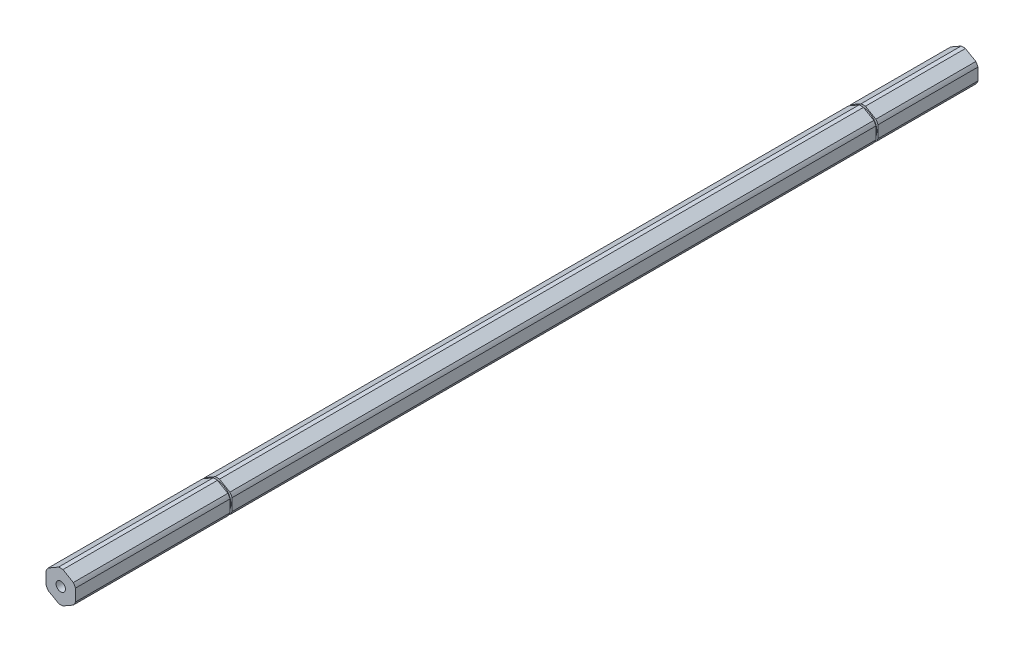
SolidWorks part; units mm, degrees
material "6061-T6 (SS)"
ref_plane "Front Plane" through (0, 0, 0) normal (0, 0, 1) x (1, 0, 0)
ref_plane "Top Plane" through (0, 0, 0) normal (0, 1, 0) x (1, 0, 0)
ref_plane "Right Plane" through (0, 0, 0) normal (1, 0, 0) x (0, 0, -1)
sketch "Sketch1" plane through (0, 0, 0) normal (0, 0, 1) x (1, 0, 0)
  line L1 (0, 7.3323) -> (-6.35, 3.6662)
  line L2 (-6.35, 3.6662) -> (-6.35, -3.6662)
  line L3 (-6.35, -3.6662) -> (0, -7.3323)
  line L4 (0, -7.3323) -> (6.35, -3.6662)
  line L5 (6.35, -3.6662) -> (6.35, 3.6662)
  line L6 (6.35, 3.6662) -> (0, 7.3323)
  circle A0 centre (0, 0) radius 6.35 construction
  circle A1 centre (0, 0) radius 6.858
  dimension "D1" = 12.7
  dimension "D2" = 13.716
extrude "Boss-Extrude1" add sketch "Sketch1" along normal mid plane 388.6403 contours L5 A1 L6 L1 L2 L3 L4 region at (0, 0, 0)
sketch "Sketch2" plane through (0, 0, 194.3202) normal (0, 0, 1) x (1, 0, 0)
  circle A0 centre (0, 0) radius 2.0193
  dimension "D1" = 4.0386
extrude "Cut-Extrude1" [suppressed] cut sketch "Sketch2" against normal through all
sketch "Sketch4" [suppressed] plane through (0, 0, 0) normal (0, 1, 0) x (1, 0, 0)
  line L0 (-2.0193, -194.3202) -> (2.0193, -194.3202) construction
  line L5 (-0.9317, -194.3202) -> (0.9317, -194.3202) construction
  line L7 (9.0297, 151.2672) -> (5.8547, 151.2672)
  line L8 (9.0297, 151.2672) -> (9.0297, 150.3782)
  line L9 (9.0297, 150.3782) -> (5.8547, 150.3782)
  line L10 (5.8547, 151.2672) -> (5.8547, 150.3782)
  line L11 (5.8547, -127.7722) -> (9.0297, -127.7722)
  line L12 (0, 194.3202) -> (0, -194.3202) construction
  line L13 (2.0193, 194.3202) -> (-2.0193, 194.3202) construction
  line L14 (5.8547, -127.7722) -> (5.8547, -126.8832)
  line L15 (5.8547, -126.8832) -> (9.0297, -126.8832)
  line L16 (9.0297, -127.7722) -> (9.0297, -126.8832)
  dimension "D1" = 0.889
  dimension "D2" = 388.6403
  dimension "D3" = 5.8547
  dimension "D4" = 43.053
  dimension "D5" = 3.175
  dimension "D6" = 3.175
  dimension "D7" = 0.889
  dimension "D8" = 66.548
revolve "Cut-Revolve4" [suppressed] cut sketch "Sketch4" angle 360 about L12
hole_wizard "#10-32 Tapped Hole1" positions "3DSketch1" profile "Sketch5" tap size "#10-32" standard "ANSI Inch"
sketch3d "3DSketch1"
  line L0 (0, 0, 194.3202) -> (0, 0, -194.3202) construction
  point P0 (0, 0, 194.3202)
sketch "Sketch5" plane through (0, 0, 194.3202) normal (1, 0, 0) x (0, -1, 0)
  line L0 (0, 0) -> (0, 13.1513)
  line L1 (0, 13.1513) -> (2.0193, 11.938)
  line L2 (2.0193, 11.938) -> (2.0193, 0)
  line L5 (2.0193, 0) -> (0, 0)
  line L10 (0, 13.1513) -> (-2.0193, 11.938) construction
  line L11 (0, -6.35) -> (0, 107.95) construction
  dimension "Tap Drill Dia." = 4.0386
  dimension "Tap Drill Depth" = 11.938
  dimension "Drill Angle" = 118
cosmetic thread "Hole Thread1" parameters "D1"=9.652, "D2"=4.826
sketch "Sketch6" plane through (0, 0, -194.3202) normal (0, 0, -1) x (-1, 0, 0)
  circle A0 centre (0, 0) radius 3.175
  dimension "D1" = 6.35
extrude "Cut-Extrude2" cut sketch "Sketch6" against normal blind 12.065
sketch "Sketch8" plane through (0, 0, 0) normal (0, 1, 0) x (1, 0, 0)
  line L0 (0, 194.3202) -> (0, -194.3202) construction
  line L1 (0.9317, 194.3202) -> (-0.9317, 194.3202) construction
  line L2 (-0.9317, -194.3202) -> (0.9317, -194.3202) construction
  line L4 (5.8547, 151.2672) -> (9.0297, 151.2672)
  line L5 (5.8547, 151.2672) -> (5.8547, 150.3782)
  line L6 (5.8547, 150.3782) -> (9.0297, 150.3782)
  line L7 (9.0297, 151.2672) -> (9.0297, 150.3782)
  line L8 (5.8547, -127.7722) -> (9.0297, -127.7722)
  line L9 (5.8547, -127.7722) -> (5.8547, -126.8832)
  line L10 (5.8547, -126.8832) -> (9.0297, -126.8832)
  line L11 (9.0297, -127.7722) -> (9.0297, -126.8832)
  dimension "D1" = 0.889
  dimension "D2" = 0.889
  dimension "D3" = 3.175
  dimension "D4" = 3.175
  dimension "D5" = 5.8547
  dimension "D6" = 43.053
  dimension "D7" = 66.548
revolve "Cut-Revolve5" cut sketch "Sketch8" angle 360 about L0
equation "\"D1@Boss-Extrude1\"=14.25"
equation "\"D1@Cut-Extrude2\"=0.25in+0.225"
